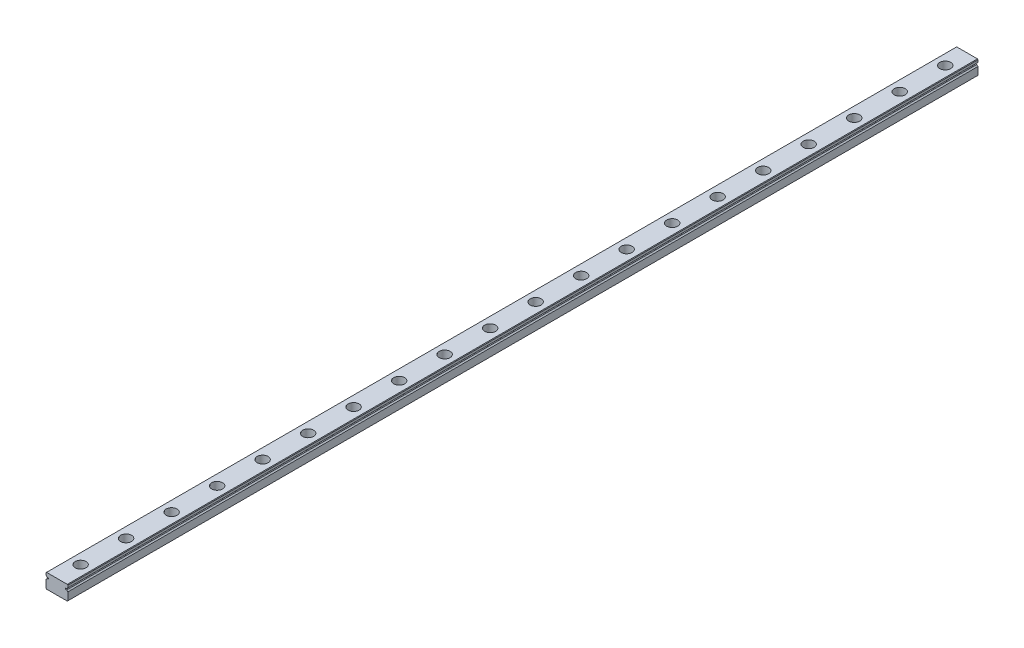
SolidWorks part; units mm, degrees
ref_plane "Спереди" through (0, 0, 0) normal (0, 0, 1) x (1, 0, 0)
ref_plane "Сверху" through (0, 0, 0) normal (0, 1, 0) x (1, 0, 0)
ref_plane "Справа" through (0, 0, 0) normal (1, 0, 0) x (0, 0, -1)
sketch "Эскиз1" plane through (0, 0, 0) normal (0, 0, 1) x (1, 0, 0)
  line L0 (-6, 3.7) -> (-5.7, 4)
  line L1 (-5.7, -4) -> (5.7, -4)
  line L2 (-6, -3.7) -> (-6, 0.549)
  line L3 (-5.7, 4) -> (5.7, 4)
  line L4 (6, -3.7) -> (6, 0.549)
  line L5 (-6, -4) -> (6, 4) construction
  line L6 (-6, 4) -> (6, -4) construction
  line L7 (-6, -3.7) -> (-5.7, -4)
  line L8 (5.7, -4) -> (6, -3.7)
  line L9 (5.7, 4) -> (6, 3.7)
  line L10 (-6, 2.451) -> (-6, 3.7)
  line L11 (-5.3546, 1.7981) -> (-4.6435, 1.7981)
  line L12 (0, 5.4188) -> (0, -5.747) construction
  line L13 (-5.3546, 1.2019) -> (-4.6435, 1.2019)
  line L14 (-4.6435, 1.7981) -> (-4.6435, 1.2019)
  line L15 (4.6435, 1.7981) -> (4.6435, 1.2019)
  line L16 (5.3546, 1.2019) -> (4.6435, 1.2019)
  line L17 (5.3546, 1.7981) -> (4.6435, 1.7981)
  line L18 (6, 2.451) -> (6, 3.7)
  line L19 (4.6435, 1.7981) -> (5.3546, 1.7981) construction
  arc A0 (-6, 0.549) -> (-5.3546, 1.2019) centre (-6.3091, 1.5) ccw
  arc A1 (-5.3546, 1.7981) -> (-6, 2.451) centre (-6.3091, 1.5) ccw
  arc A2 (5.3546, 1.7981) -> (6, 2.451) centre (6.3091, 1.5) cw
  arc A3 (6, 0.549) -> (5.3546, 1.2019) centre (6.3091, 1.5) cw
  point P0 (0, 0)
extrude "Бобышка-Вытянуть1" add sketch "Эскиз1" along normal blind 500
sketch "Эскиз2" plane through (0, 4, 0) normal (0, 1, 0) x (1, 0, 0)
  line L0 (0, 0) -> (0, -26.2396) construction
  line L1 (5.7, 0) -> (-5.7, 0) construction
  line L2 (-3.8306, -12) -> (3.8306, -12) construction
  circle A0 centre (0, -12) radius 3
  circle A1 centre (0, -12) radius 1.75
  dimension "D2" = 3.5
  dimension "D3" = 6
  dimension "D1" = 12
extrude "Вырез-Вытянуть1" cut sketch "Эскиз2" against normal blind 4.5
extrude "Вырез-Вытянуть2" cut sketch "Эскиз2<2>" against normal through all contours A1 region at (0, 4, 12)
sketch "Эскиз2<2>" plane through (0, 4, 0) normal (0, 1, 0) x (1, 0, 0) same geometry as "Эскиз2"
pattern_linear "Линейный массив1" count 20 spacing 25 along (0, 0, 1) of "Вырез-Вытянуть1", "Вырез-Вытянуть2"
